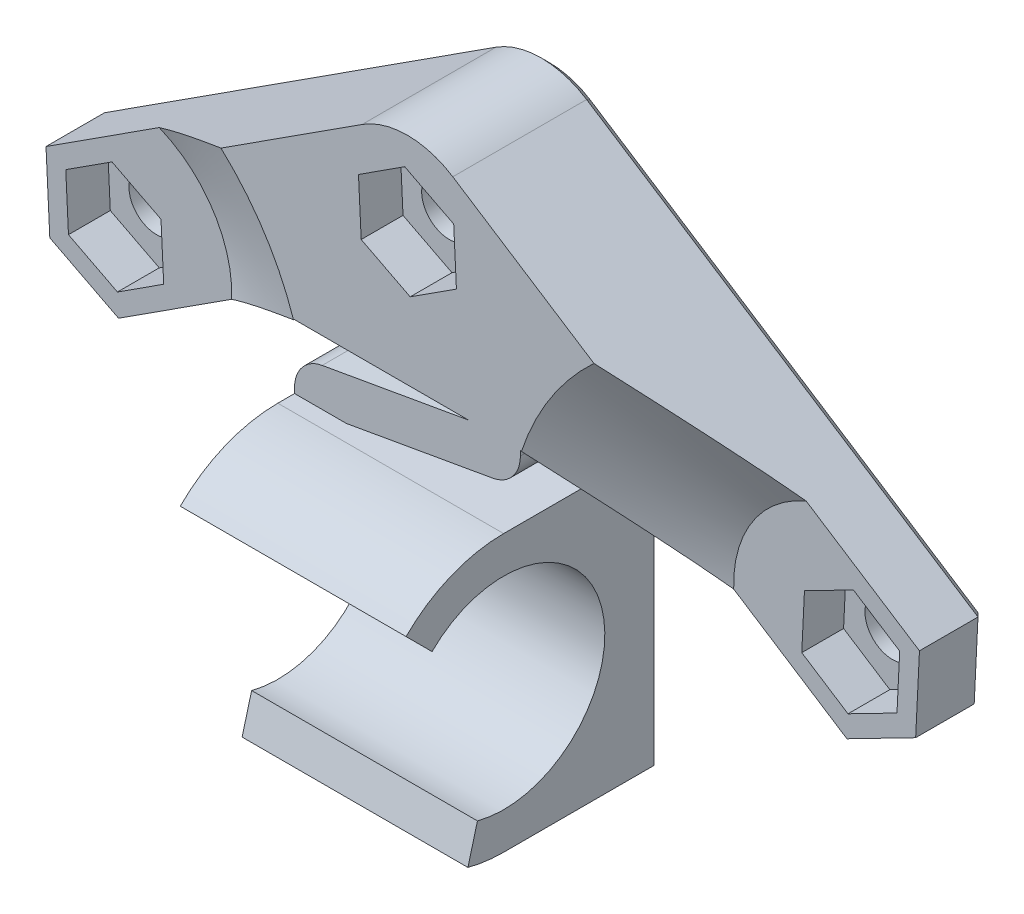
SolidWorks part; units mm, degrees
material "ABS"
ref_plane "Front Plane" through (0, 0, 0) normal (0, 0, 1) x (1, 0, 0)
ref_plane "Top Plane" through (0, 0, 0) normal (0, 1, 0) x (1, 0, 0)
ref_plane "Right Plane" through (0, 0, 0) normal (1, 0, 0) x (0, 0, -1)
sketch "Sketch1" plane through (0, 0, 0) normal (-1, 0, 0) x (0, 0, 1)
  line L0 (-9.5, 8.25) -> (-9.5, -8.25)
  line L1 (0, 8.25) -> (-9.5, 8.25)
  line L2 (0, -8.25) -> (-9.5, -8.25)
  arc A4 (0, -8.25) -> (0, 8.25) centre (0, 0) ccw
  dimension "D2" = 16.5
  dimension "D3" = 9.5
extrude "Boss-Extrude1" add sketch "Sketch1" along normal blind 13.5
hole_wizard "Ø2.7 (2.7) Diameter Hole1" [suppressed] positions "Sketch5" profile "Sketch4" hole size "Ø2.7" standard "Ansi Metric"
sketch "Sketch5" [suppressed] plane through (-9.5, 0, 0) normal (-1, 0, 0) x (0, 0, 1)
  line L1 (2.5, -5) -> (11, -5) construction
  line L2 (2.5, -5) -> (2.5, 5) construction
  line L3 (2.5, 5) -> (11, 5) construction
  line L4 (11, -5) -> (11, 5) construction
  line L5 (0, 0) -> (2.5, 0) construction
  line L7 (-8.25, 0) -> (8.25, 0) construction
  line L10 (13.5, 0) -> (11, 0) construction
  line L11 (-8.25, 13.5) -> (8.25, 13.5) construction
  point P0 (2.5, -5)
  point P89 (2.5, 5)
  point P91 (11, 5)
  point P93 (11, -5)
  dimension "D1" = 2.5
  dimension "D2" = 10
sketch "Sketch4" plane through (-9.5, -5, 2.5) normal (0, 1, 0) x (0, 0, 1)
  line L0 (0, 0) -> (0, 4.8112)
  line L1 (0, 4.8112) -> (1.35, 4)
  line L2 (1.35, 4) -> (1.35, 0)
  line L5 (1.35, 0) -> (0, 0)
  line L10 (0, 4.8112) -> (-1.35, 4) construction
  line L11 (0, -6.35) -> (0, 107.95) construction
  dimension "Hole Dia." = 2.7
  dimension "Hole Depth" = 4
  dimension "Drill Angle" = 118
sketch "Sketch7" plane through (-13.5, 0, 0) normal (-1, 0, 0) x (0, 0, 1)
  line L0 (13.4819, 13.4819) -> (4.278, 4.278)
  line L1 (1.5659, -5.8439) -> (4.9347, -18.4166)
  line L2 (4.9347, -18.4166) -> (13.4819, 13.4819)
  line L3 (0, 0) -> (4.278, 4.278) construction
  line L4 (0, 0) -> (1.5659, -5.8439) construction
  line L5 (0, 0) -> (0, 14.6798) construction
  arc A0 (4.278, 4.278) -> (1.5659, -5.8439) centre (0, 0) ccw
  dimension "D3" = 6.05
  dimension "D1" = 120
  dimension "D2" = 45
extrude "Cut-Extrude1" cut sketch "Sketch7" against normal through all
ref_plane "Plane1" through (0, 0, -5.8439) normal (0, 0, -1) x (-1, 0, 0)
sketch "Sketch14" plane through (0, 0, -9.5) normal (0, 0, -1) x (-1, 0, 0)
  line L0 (6.75, -8.25) -> (6.75, 25.8362) construction
  line L1 (13.5, -8.25) -> (0, -8.25) construction
  line L2 (6.75, 7) -> (-15.25, 7) construction
  line L3 (4.0398, 24.2018) -> (-19.3588, 9.1097)
  line L4 (-17.4181, 10.3614) -> (-13.0819, 3.6386) construction
  line L5 (-15.0226, 2.3868) -> (0, 12.0764)
  line L6 (13.5, 8.25) -> (13.5, 12.0764)
  line L7 (0, 8.25) -> (0, 12.0764)
  line L8 (0, 8.25) -> (0, -8.25) construction
  line L9 (13.5, 8.25) -> (0, 8.25) construction
  line L10 (0, 8.25) -> (13.5, 8.25)
  line L12 (28.5226, 2.3868) -> (13.5, 12.0764)
  line L13 (9.4602, 24.2018) -> (32.8588, 9.1097)
  line L14 (-19.1315, 4.4965) -> (-15.0226, 2.3868)
  line L19 (-19.3588, 9.1097) -> (-19.1315, 4.4965)
  line L20 (32.6315, 4.4965) -> (32.8588, 9.1097)
  line L25 (28.5226, 2.3868) -> (32.6315, 4.4965)
  line L26 (24.6412, 4.8903) -> (28.5226, 2.3868)
  line L27 (32.8588, 9.1097) -> (28.9774, 11.6132)
  line L28 (28.9774, 11.6132) -> (24.8685, 9.5035)
  line L29 (24.8685, 9.5035) -> (24.6412, 4.8903)
  line L30 (-15.4774, 11.6132) -> (-19.3588, 9.1097)
  line L31 (-15.0226, 2.3868) -> (-11.1412, 4.8903)
  line L32 (-11.1412, 4.8903) -> (-11.3685, 9.5035)
  line L33 (-11.3685, 9.5035) -> (-15.4774, 11.6132)
  circle A0 centre (6.75, 20) radius 1.65
  arc A1 (9.4602, 24.2018) -> (4.0398, 24.2018) centre (6.75, 20) ccw
  circle A2 centre (-15.25, 7) radius 1.65
  circle A4 centre (28.75, 7) radius 1.65
  circle A6 centre (-15.25, 7) radius 4 construction
  circle A7 centre (28.75, 7) radius 4 construction
  point P24 (6.75, 8.25)
  dimension "D1" = 3.3
  dimension "D3" = 5
  dimension "D6" = 3.3
  dimension "D2" = 20
  dimension "D4" = 22
  dimension "D5" = 13
extrude "Boss-Extrude3" add sketch "Sketch14" against normal blind 8.5
sketch "Sketch15" plane through (0, 0, -1) normal (0, 0, 1) x (1, 0, 0)
  line L0 (0, 8.25) -> (-10.4017, 8.25)
  line L1 (0, 8.25) -> (-13.5, 8.25) construction
  line L2 (-10.4017, 8.25) -> (0, 10.0841)
  line L3 (0, 12.0764) -> (0, 8.25) construction
  line L4 (0, 10.0841) -> (0, 8.25)
  line L6 (-13.5, 8.25) -> (-13.5, 12.0764) construction
  line L7 (-13.5, 10.2423) -> (-13.5, 12.0764)
  line L8 (-13.5, 12.0764) -> (-3.0983, 12.0764)
  line L9 (-3.0983, 12.0764) -> (-13.5, 10.2423)
  dimension "D1" = 2.5
  dimension "D2" = 10
extrude "Cut-Extrude7" cut sketch "Sketch15" against normal through all
fillet "Fillet2" radius 2 2 edges at (0, 10.0841, -5.25) (-13.5, 10.2423, -5.25)
sketch "Sketch17" plane through (0, 0, -1) normal (0, 0, 1) x (1, 0, 0)
  line L1 (19.1315, 4.4965) -> (19.3588, 9.1097)
  line L2 (19.3588, 9.1097) -> (17.4181, 10.3614)
  line L3 (-32.6315, 4.4965) -> (-28.5226, 2.3868)
  line L4 (-28.5226, 2.3868) -> (-26.5819, 3.6386)
  line L5 (13.0819, 3.6386) -> (15.0226, 2.3868)
  line L6 (15.0226, 2.3868) -> (19.1315, 4.4965)
  line L7 (13.423, 10.5584) -> (11.3685, 9.5035)
  line L8 (11.2549, 7.1969) -> (11.1412, 4.8903)
  line L11 (-30.9181, 10.3614) -> (-32.8588, 9.1097)
  line L12 (-32.8588, 9.1097) -> (-32.6315, 4.4965)
  line L13 (-24.6412, 4.8903) -> (-24.8685, 9.5035)
  line L14 (-24.8685, 9.5035) -> (-28.9774, 11.6132)
  arc A0 (-26.5819, 3.6386) -> (-30.9181, 10.3614) centre (-28.75, 7) ccw
  arc A1 (17.4181, 10.3614) -> (13.0819, 3.6386) centre (15.25, 7) ccw
  circle A2 centre (15.25, 7) radius 4 construction
  circle A3 centre (-28.75, 7) radius 4 construction
extrude "Cut-Extrude9" cut sketch "Sketch17" against normal offset from surface (4.5 mm away) 4 up to face at (-6.3947, 8.3194, -9.5)
chamfer "Chamfer2" distance 12 distance2 6 1 edges at (-25.3886, 9.1681, -1)
chamfer "Chamfer3" distance 12 distance2 6 1 edges at (11.8886, 9.1681, -1)
sketch "Sketch19" plane through (0, 0, -5.5) normal (0, 0, 1) x (1, 0, 0)
  line L0 (-32.8588, 9.1097) -> (-26.0906, 13.4752) construction
  line L1 (-31.5155, 5.2162) -> (-28.588, 3.7131)
  line L2 (-28.588, 3.7131) -> (-25.8224, 5.4969)
  line L3 (-25.8224, 5.4969) -> (-25.9845, 8.7838)
  line L4 (-25.9845, 8.7838) -> (-28.912, 10.2869)
  line L5 (-28.912, 10.2869) -> (-31.6776, 8.5031)
  line L6 (-31.6776, 8.5031) -> (-31.5155, 5.2162)
  line L7 (18.0155, 5.2162) -> (18.1776, 8.5031)
  line L8 (18.1776, 8.5031) -> (15.412, 10.2869)
  line L9 (15.412, 10.2869) -> (12.4845, 8.7838)
  line L10 (12.4845, 8.7838) -> (12.3224, 5.4969)
  line L11 (12.3224, 5.4969) -> (15.088, 3.7131)
  line L12 (15.088, 3.7131) -> (18.0155, 5.2162)
  line L13 (12.5906, 13.4752) -> (19.3588, 9.1097) construction
  circle A0 centre (-28.75, 7) radius 2.85 construction
  circle A1 centre (15.25, 7) radius 2.85 construction
  circle A3 centre (-28.75, 7) radius 1.65 construction
  circle A4 centre (15.25, 7) radius 1.65 construction
  dimension "D1" = 5.7
extrude "Cut-Extrude11" cut sketch "Sketch19" against normal blind 2.5
sketch "Sketch20" plane through (0, 0, -1) normal (0, 0, 1) x (1, 0, 0)
  line L0 (-25.8224, 5.4969) -> (-25.9845, 8.7838) construction
  line L1 (-9.5155, 18.2162) -> (-6.588, 16.7131)
  line L2 (-6.588, 16.7131) -> (-3.8224, 18.4969)
  line L3 (-3.8224, 18.4969) -> (-3.9845, 21.7838)
  line L4 (-3.9845, 21.7838) -> (-6.912, 23.2869)
  line L5 (-6.912, 23.2869) -> (-9.6776, 21.5031)
  line L6 (-9.6776, 21.5031) -> (-9.5155, 18.2162)
  circle A0 centre (-6.75, 20) radius 2.85 construction
  dimension "D1" = 5.7
extrude "Cut-Extrude12" cut sketch "Sketch20" against normal blind 2.5
chamfer "Chamfer4" distance 0.5 angle 45 3 edges at (13.6, 7, -9.5) (-8.4, 20, -9.5) (-27.1, 7, -9.5)
chamfer "Chamfer8" distance 0.5 angle 45 12 edges at (-13.5, 0.157, -9.5) (-21.0113, 7.2316, -9.5) (-30.577, 3.4416, -9.5) (-32.7451, 6.8031, -9.5) (-21.1595, 16.6557, -9.5) (-6.75, 25, -9.5) (7.6595, 16.6557, -9.5) (19.2451, 6.8031, -9.5) (17.077, 3.4416, -9.5) (7.5113, 7.2316, -9.5) (0, 0, -9.5) (-6.75, -8.25, -9.5)
